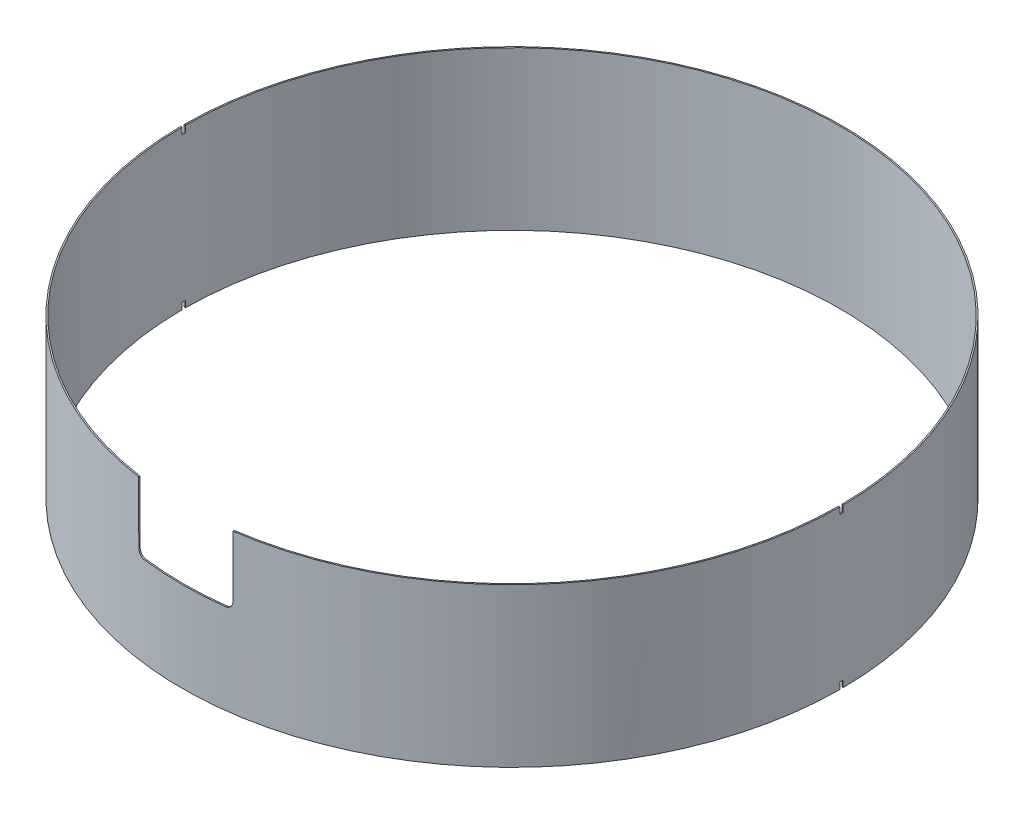
SolidWorks part; units mm, degrees
ref_plane "Front Plane" through (0, 0, 0) normal (0, 0, 1) x (1, 0, 0)
ref_plane "Top Plane" through (0, 0, 0) normal (0, 1, 0) x (1, 0, 0)
ref_plane "Right Plane" through (0, 0, 0) normal (1, 0, 0) x (0, 0, -1)
sketch "Эскиз1" plane through (0, 0, 0) normal (0, 1, 0) x (1, 0, 0)
  circle A0 centre (0, 0) radius 50
  circle A1 centre (0, 0) radius 49.8
extrude "Бобышка-Вытянуть1" add sketch "Эскиз1" along normal blind 24
sketch "Эскиз2" plane through (0, 0, 0) normal (0, 0, 1) x (1, 0, 0)
  line L0 (-7.1302, 13.65) -> (-7.1588, 24)
  line L1 (7.1588, 24) -> (7.1302, 13.65)
  line L2 (7.1302, 13.65) -> (-7.1302, 13.65)
  line L3 (-7.1588, 24) -> (7.1588, 24)
  line L4 (49.8, 24) -> (-49.8, 24) construction
  point P4 (0, 24)
extrude "Вырез-Вытянуть1" cut sketch "Эскиз2" along normal blind 52
sketch "Эскиз3" plane through (0, 0, 0) normal (1, 0, 0) x (0, 0, -1)
  line L0 (0, 24) -> (0.25, 24)
  line L8 (0, 24) -> (-0.25, 24)
  line L9 (-0.25, 24) -> (-0.25, 23)
  line L10 (-0.25, 23) -> (0.25, 23)
  line L11 (0.25, 23) -> (0.25, 24)
  line L12 (0, 0) -> (0, 24) construction
  line L14 (0, 12) -> (3.0275, 12) construction
  line L15 (0.25, 1) -> (0.25, 0)
  line L16 (-0.25, 1) -> (0.25, 1)
  line L17 (-0.25, 0) -> (-0.25, 1)
  line L18 (0, 0) -> (-0.25, 0)
  line L19 (0, 0) -> (0.25, 0)
extrude "Вырез-Вытянуть2" cut sketch "Эскиз3" against normal blind 52 and the other way blind 52
fillet "Скругление1" radius 1 2 edges at (7.1302, 13.65, 49.388) (-7.1302, 13.65, 49.388)
